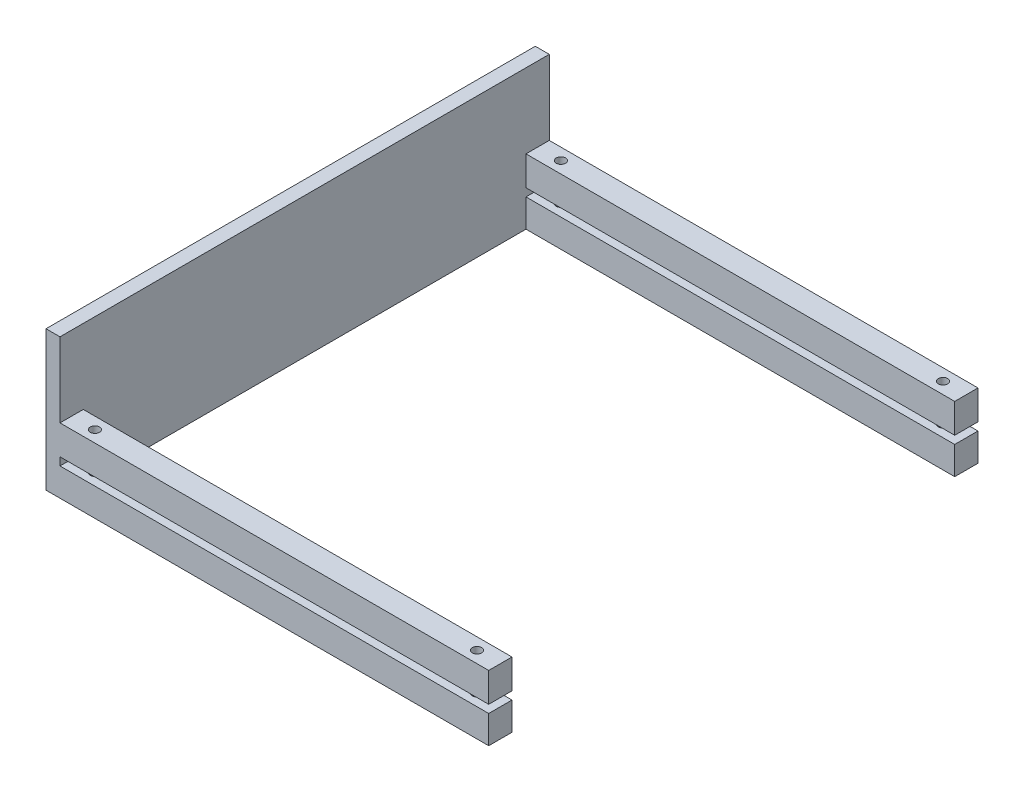
SolidWorks part; units mm, degrees
ref_plane "Front Plane" through (0, 0, 0) normal (0, 0, 1) x (1, 0, 0)
ref_plane "Top Plane" through (0, 0, 0) normal (0, 1, 0) x (1, 0, 0)
ref_plane "Right Plane" through (0, 0, 0) normal (1, 0, 0) x (0, 0, -1)
sketch "Sketch1" plane through (0, 0, 0) normal (0, 0, 1) x (1, 0, 0)
  line L0 (0, 16) -> (0, 0)
  line L1 (0, 16) -> (-3, 16)
  line L2 (-3, 16) -> (-3, -14)
  line L3 (-3, -14) -> (92, -14)
  line L4 (92, -14) -> (92, 0)
  line L5 (92, 0) -> (0, 0)
  dimension "D1" = 95
  dimension "D2" = 14
  dimension "D3" = 3
  dimension "D4" = 30
extrude "Boss-Extrude1" add sketch "Sketch1" against normal blind 105
sketch "Sketch2" plane through (0, 0, 0) normal (1, 0, 0) x (0, 0, -1)
  line L10 (0, -6.3) -> (5, -6.3)
  line L11 (0, -14) -> (0, 0) construction
  line L12 (5, -6.3) -> (5, 0)
  line L13 (105, 0) -> (0, 0) construction
  line L14 (5, 0) -> (100, 0)
  line L25 (100, 0) -> (100, -6.3)
  line L27 (100, -6.3) -> (105, -6.3)
  line L28 (105, -14) -> (105, 0) construction
  line L29 (105, -6.3) -> (105, -8)
  line L30 (105, -8) -> (100, -8)
  line L31 (100, -8) -> (100, -14)
  line L32 (105, -14) -> (0, -14) construction
  line L33 (100, -14) -> (5, -14)
  line L34 (5, -14) -> (5, -8)
  line L35 (5, -8) -> (0, -8)
  line L36 (0, -8) -> (0, -6.3)
  dimension "D1" = 1.7
  dimension "D2" = 6
  dimension "D3" = 5
  dimension "D4" = 5
extrude "Cut-Extrude1" cut sketch "Sketch2" along normal through all contours L12 L14 L25 L27 L29 L30 L31 L33 L34 L35 L36 L10
sketch "Sketch3" plane through (0, 0, 0) normal (0, 1, 0) x (1, 0, 0)
  line L0 (92, 105) -> (92, 100) construction
  line L1 (92, 5) -> (92, 0) construction
  line L2 (0, 5) -> (0, 0) construction
  circle A0 centre (87, 102.5) radius 1
  circle A1 centre (5, 102.5) radius 1
  circle A2 centre (5, 2.5) radius 1
  circle A3 centre (87, 2.5) radius 1
  point P17 (92, 102.5)
  point P21 (92, 2.5)
  dimension "D1" = 2
  dimension "D2" = 5
  dimension "D3" = 5
extrude "Cut-Extrude2" cut sketch "Sketch3" against normal through all
